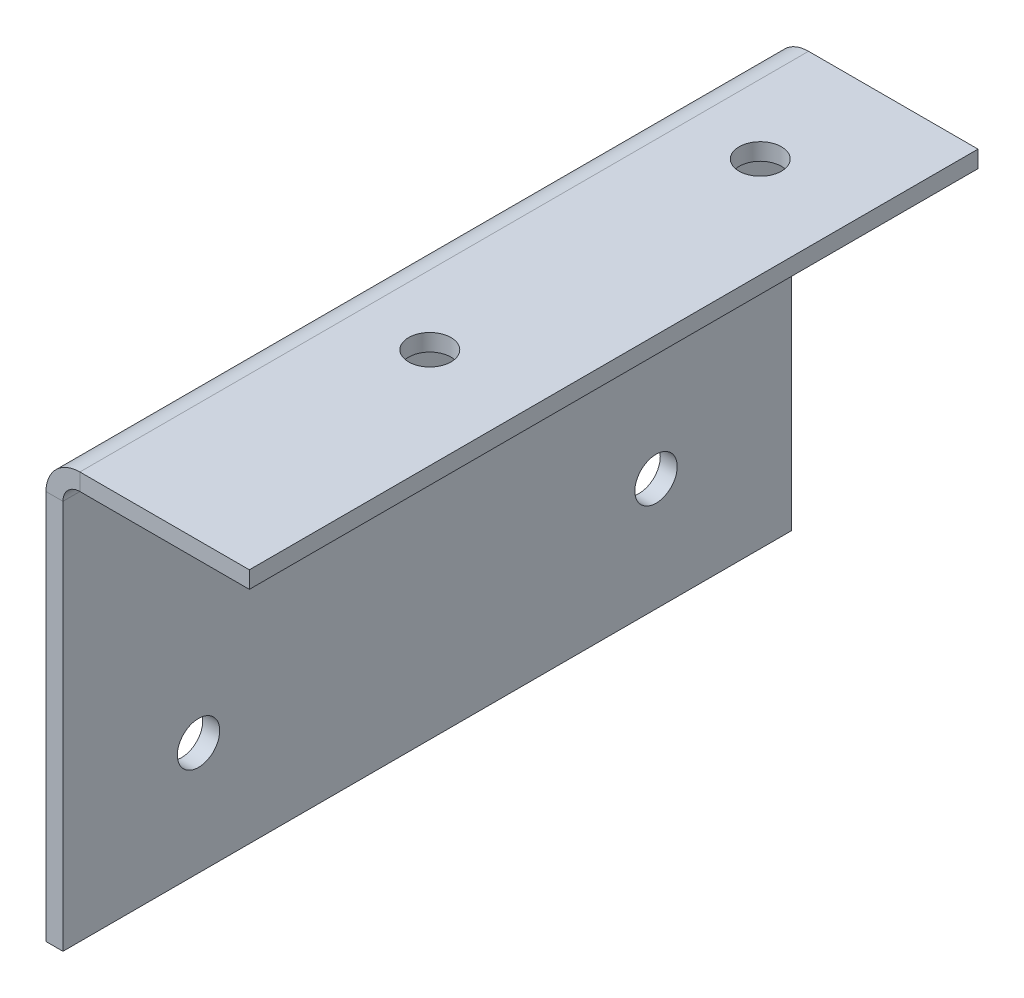
SolidWorks part; units mm, degrees
note: The reader was unsure of these and kept them because the rebuilt part matched: flange length of "Edge-Flange1".
ref_plane "Front Plane" through (0, 0, 0) normal (0, 0, 1) x (1, 0, 0)
ref_plane "Top Plane" through (0, 0, 0) normal (0, 1, 0) x (1, 0, 0)
ref_plane "Right Plane" through (0, 0, 0) normal (1, 0, 0) x (0, 0, -1)
sketch "Sketch1" plane through (0, 0, 0) normal (1, 0, 0) x (0, 0, -1)
  line L1 (-21.5, 12.5) -> (21.5, 12.5)
  line L2 (-21.5, 12.5) -> (-21.5, -12.5)
  line L3 (-21.5, -12.5) -> (21.5, -12.5)
  line L4 (21.5, 12.5) -> (21.5, -12.5)
  line L5 (-21.5, 12.5) -> (21.5, -12.5) construction
  line L6 (-21.5, -12.5) -> (21.5, 12.5) construction
  point P0 (0, 0)
  dimension "D1" = 43
  dimension "D2" = 25
base flange "Base-Flange1" sketch "Sketch1" thickness 1 reverse thickness direction no parameters "D1"=2
edge flange "Edge-Flange1" sketch "Sketch10" flange angle 90 flange length 12 flange position material inside bend radius 1 thickness 1 relief rectangular parameters "D6"=10
sketch "Sketch10" plane through (0, 12.5, 0) normal (0, 1, 0) x (0, 0, 1)
  line L0 (-21.5, 0) -> (21.5, 0) construction
  line L1 (-21.5, 0) -> (21.5, 0)
  line L2 (-21.5, 0) -> (-21.5, 11)
  line L3 (-21.5, 11) -> (21.5, 11)
  line L4 (21.5, 11) -> (21.5, 0)
bend "EdgeBend1" bend radius 1 bend angle 90 parameters "D5"=1
hole_wizard "Tap Drill for M3 Tap1" positions "Sketch11" profile "Sketch12" hole size "M3" standard "ISO" end condition through all
sketch "Sketch11" plane through (-360.4715, 12.5, -232.458) normal (0, 1, 0) x (-1, 0, 0)
  point P0 (-365.5515, 237.3872)
  point P2 (-365.5515, 217.8872)
sketch "Sketch12" plane through (5.08, 12.5, 4.9292) normal (1, 0, 0) x (0, 0, 1)
  line L0 (0, 0) -> (0, 25)
  line L1 (0, 25) -> (1.25, 25)
  line L2 (1.25, 25) -> (1.25, 0)
  line L3 (1.25, 0) -> (0, 0)
  line L4 (0, -6.35) -> (0, 107.95) construction
  dimension "Thru Hole Dia." = 2.5
  dimension "Thru Hole Depth" = 25
hole_wizard "Tap Drill for M3 Tap2" positions "Sketch13" profile "Sketch14" hole size "M3" standard "ISO"
sketch "Sketch13" plane through (2, 426.0945, -232.458) normal (1, 0, 0) x (0, 1, 0)
  point P0 (-431.9425, 218.958)
  point P2 (-431.9425, 245.958)
sketch "Sketch14" plane through (2, -5.848, -13.5) normal (0, 1, 0) x (0, 0, -1)
  line L0 (0, 0) -> (0, 10.7511)
  line L1 (0, 10.7511) -> (1.25, 10)
  line L2 (1.25, 10) -> (1.25, 0)
  line L3 (1.25, 0) -> (0, 0)
  line L4 (0, 10.7511) -> (-1.25, 10) construction
  line L5 (0, -6.35) -> (0, 107.95) construction
  dimension "Hole Dia." = 2.5
  dimension "Hole Depth" = 10
  dimension "Drill Angle" = 118
sketch "Bend-Lines1" [suppressed] plane through (0, 0, 0) normal (0, 1, 0) x (1, 0, 0)
sketch "Bounding-Box1" [suppressed] plane through (0, 0, 0) normal (0, 1, 0) x (1, 0, 0)
sheet metal parameters "Sheet-Metal12" thickness 1 parameters "D1"=2
flat pattern "Flat-Pattern12" [suppressed]
sketch "Bend-Lines2" plane through (0, 0, 0) normal (0, 1, 0) x (1, 0, 0)
sketch3d "Bounding-Box2" [suppressed]
  line L0 (20.5442, -7.6846, 0) -> (-20.5442, -7.6846, 0) construction
  line L1 (20.5442, 7.6846, 0) -> (-20.5442, 7.6846, 0) construction
  line L2 (20.5442, -7.6846, 0) -> (20.5442, 7.6846, 0) construction
  line L3 (-20.5442, -7.6846, 0) -> (-20.5442, 7.6846, 0) construction
sheet metal parameters "Sheet-Metal13" thickness 1 parameters "D1"=2
flat pattern "Flat-Pattern12"
sketch "Bend-Lines2" plane through (0, 0, 0) normal (1, 0, 0) x (0, 0, -1)
  line L0 (21.5, 11.6781) -> (-21.5, 11.6781) construction
  line L1 (21.5, 11.6781) -> (-21.5, 11.6781) construction
sketch3d "Bounding-Box2" [suppressed]
  line L0 (-21.5, -12.5, 0) -> (21.5, -12.5, 0) construction
  line L1 (-21.5, 22.8562, 0) -> (21.5, 22.8562, 0) construction
  line L2 (-21.5, -12.5, 0) -> (-21.5, 22.8562, 0) construction
  line L3 (21.5, -12.5, 0) -> (21.5, 22.8562, 0) construction
bend of the flat pattern "Flatten-<EdgeBend1>1"
sheet metal parameters "Sheet-Metal14" thickness 1 parameters "D1"=2
flat pattern "Flat-Pattern12"
sketch "Bend-Lines2" plane through (0, 0, 0) normal (1, 0, 0) x (0, 0, -1)
  line L0 (21.5, 11.6781) -> (-21.5, 11.6781) construction
  line L1 (21.5, 11.6781) -> (-21.5, 11.6781) construction
sketch3d "Bounding-Box2" [suppressed]
  line L0 (-21.5, -12.5, 0) -> (21.5, -12.5, 0) construction
  line L1 (-21.5, 22.8562, 0) -> (21.5, 22.8562, 0) construction
  line L2 (-21.5, -12.5, 0) -> (-21.5, 22.8562, 0) construction
  line L3 (21.5, -12.5, 0) -> (21.5, 22.8562, 0) construction
bend of the flat pattern "Flatten-<EdgeBend1>1"
sheet metal parameters "Sheet-Metal15" thickness 1 parameters "D1"=2
flat pattern "Flat-Pattern12"
sketch "Bend-Lines2" plane through (0, 0, 0) normal (1, 0, 0) x (0, 0, -1)
  line L0 (21.5, 11.6781) -> (-21.5, 11.6781) construction
  line L1 (21.5, 11.6781) -> (-21.5, 11.6781) construction
sketch3d "Bounding-Box2" [suppressed]
  line L0 (-21.5, -12.5, 0) -> (21.5, -12.5, 0) construction
  line L1 (-21.5, 22.8562, 0) -> (21.5, 22.8562, 0) construction
  line L2 (-21.5, -12.5, 0) -> (-21.5, 22.8562, 0) construction
  line L3 (21.5, -12.5, 0) -> (21.5, 22.8562, 0) construction
bend of the flat pattern "Flatten-<EdgeBend1>1"
